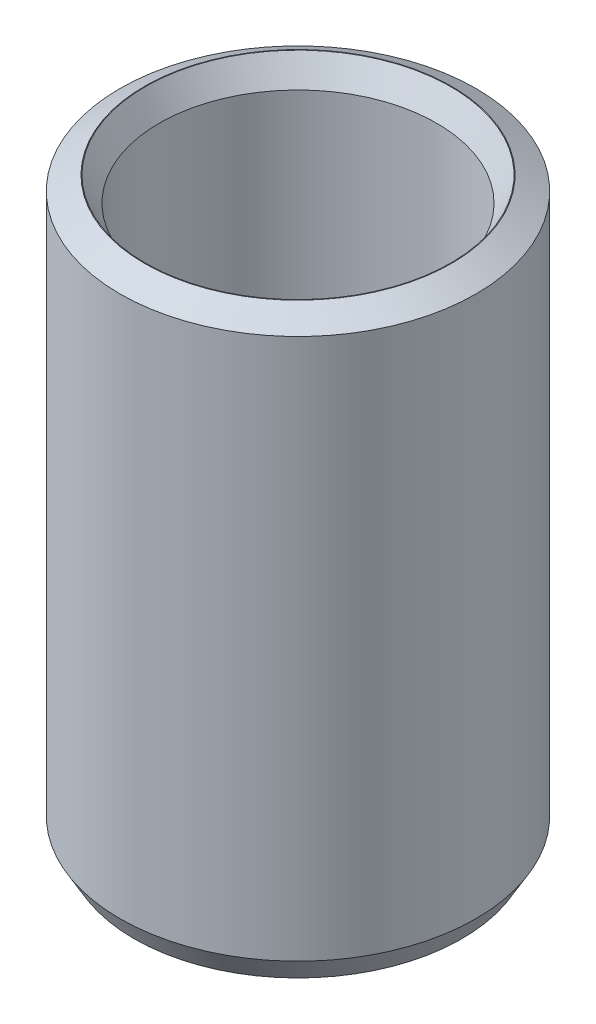
SolidWorks part; units mm, degrees
ref_plane "Front Plane" through (0, 0, 0) normal (0, 0, 1) x (1, 0, 0)
ref_plane "Top Plane" through (0, 0, 0) normal (0, 1, 0) x (1, 0, 0)
ref_plane "Right Plane" through (0, 0, 0) normal (1, 0, 0) x (0, 0, -1)
sketch "Sketch1" plane through (0, 0, 0) normal (0, 1, 0) x (1, 0, 0)
  circle A0 centre (0, 0) radius 30
  dimension "SLEEVE_OD" = 60
extrude "Boss-Extrude1" add sketch "Sketch1" along normal blind 97.7055
sketch "Sketch2" plane through (0, 0, 0) normal (0, 1, 0) x (1, 0, 0)
  circle A0 centre (0, 0) radius 23.3681
  dimension "BORE_D" = 46.7362
extrude "Cut-Extrude1" cut sketch "Sketch2" along normal through all
chamfer "Chamfer1" distance 2.3843 angle 60 4 edges at (0, 97.7055, 23.3681) (0, 0, 23.3681) (0, 0, 30) (0, 97.7055, 30) first distance on face at (0, 97.7055, 23.3681) first distance on face at (0, 0, 23.3681) first distance on face at (0, 97.7055, 30)
